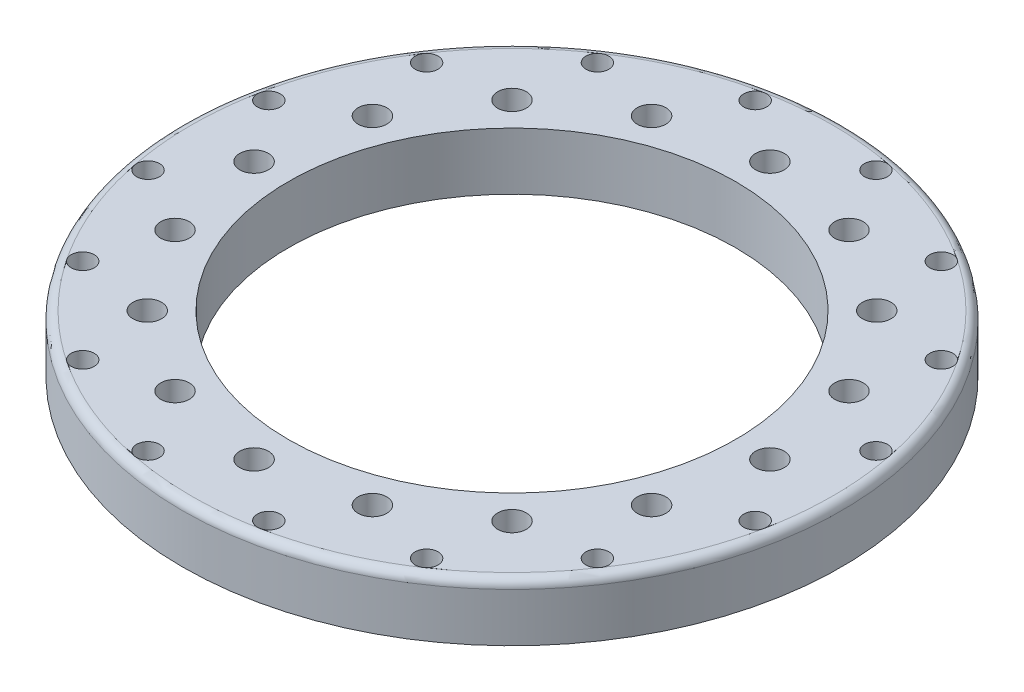
SolidWorks part; units mm, degrees
ref_plane "Front Plane" through (0, 0, 0) normal (0, 0, 1) x (1, 0, 0)
ref_plane "Top Plane" through (0, 0, 0) normal (0, 1, 0) x (1, 0, 0)
ref_plane "Right Plane" through (0, 0, 0) normal (1, 0, 0) x (0, 0, -1)
sketch "Sketch1" plane through (0, 0, 0) normal (0, 1, 0) x (1, 0, 0)
  line L0 (-10.5349, 52.9624) -> (0, 0) construction
  line L1 (0, 0) -> (24.6214, 0) construction
  circle A12 centre (0, 0) radius 39
  circle A13 centre (0, 0) radius 57.5
  circle A14 centre (0, 0) radius 54 construction
  circle A15 centre (-10.5349, 52.9624) radius 2
  circle A16 centre (10.5349, 52.9624) radius 2
  circle A17 centre (30.0008, 44.8994) radius 2
  circle A18 centre (44.8994, 30.0008) radius 2
  circle A19 centre (52.9624, 10.5349) radius 2
  circle A20 centre (52.9624, -10.5349) radius 2
  circle A21 centre (44.8994, -30.0008) radius 2
  circle A22 centre (30.0008, -44.8994) radius 2
  circle A23 centre (10.5349, -52.9624) radius 2
  circle A24 centre (-10.5349, -52.9624) radius 2
  circle A25 centre (-30.0008, -44.8994) radius 2
  circle A26 centre (-44.8994, -30.0008) radius 2
  circle A47 centre (-52.9624, -10.5349) radius 2
  circle A48 centre (-52.9624, 10.5349) radius 2
  circle A49 centre (-44.8994, 30.0008) radius 2
  circle A50 centre (-30.0008, 44.8994) radius 2
  point P21 (0, 0)
  point P28 (0, 0)
  point P56 (0, 0)
  point P60 (0, 0)
  dimension "D1" = 101.25
  dimension "D4" = 115
  dimension "D5" = 78
  dimension "D6" = 108
  dimension "D7" = 4
  dimension "D8" = 16
extrude "Boss-Extrude1" add sketch "Sketch1" along normal blind 10
sketch "Sketch2" plane through (0, 10, 0) normal (0, 1, 0) x (1, 0, 0)
  circle A0 centre (0, 0) radius 45 construction
  circle A1 centre (0, 45) radius 2.5
  circle A2 centre (17.2208, 41.5746) radius 2.5
  circle A3 centre (31.8198, 31.8198) radius 2.5
  circle A4 centre (41.5746, 17.2208) radius 2.5
  circle A5 centre (45, 0) radius 2.5
  circle A6 centre (41.5746, -17.2208) radius 2.5
  circle A7 centre (31.8198, -31.8198) radius 2.5
  circle A8 centre (17.2208, -41.5746) radius 2.5
  circle A9 centre (0, -45) radius 2.5
  circle A10 centre (-17.2208, -41.5746) radius 2.5
  circle A11 centre (-31.8198, -31.8198) radius 2.5
  circle A12 centre (-41.5746, -17.2208) radius 2.5
  circle A13 centre (-45, 0) radius 2.5
  circle A14 centre (-41.5746, 17.2208) radius 2.5
  circle A15 centre (-31.8198, 31.8198) radius 2.5
  circle A16 centre (-17.2208, 41.5746) radius 2.5
  point P27 (0, 0)
  dimension "D1" = 90
  dimension "D2" = 5
  dimension "D3" = 16
extrude "Cut-Extrude1" cut sketch "Sketch2" against normal blind 10
sketch "Sketch4" plane through (0, 0, 0) normal (0, 1, 0) x (1, 0, 0)
  circle A0 centre (0, 0) radius 45 construction
  circle A1 centre (0, 45) radius 5
  circle A2 centre (0, 45) radius 2.5
  circle A3 centre (17.2208, 41.5746) radius 2.5
  circle A4 centre (31.8198, 31.8198) radius 2.5
  circle A5 centre (41.5746, 17.2208) radius 2.5
  circle A6 centre (45, 0) radius 2.5
  circle A7 centre (41.5746, -17.2208) radius 2.5
  circle A8 centre (31.8198, -31.8198) radius 2.5
  circle A9 centre (17.2208, -41.5746) radius 2.5
  circle A10 centre (0, -45) radius 2.5
  circle A11 centre (-17.2208, -41.5746) radius 2.5
  circle A12 centre (-31.8198, -31.8198) radius 2.5
  circle A13 centre (17.2208, 41.5746) radius 5
  circle A14 centre (31.8198, 31.8198) radius 5
  circle A15 centre (41.5746, 17.2208) radius 5
  circle A16 centre (45, 0) radius 5
  circle A17 centre (41.5746, -17.2208) radius 5
  circle A18 centre (31.8198, -31.8198) radius 5
  circle A19 centre (17.2208, -41.5746) radius 5
  circle A20 centre (0, -45) radius 5
  circle A21 centre (-17.2208, -41.5746) radius 5
  circle A22 centre (-31.8198, -31.8198) radius 5
  circle A23 centre (-41.5746, -17.2208) radius 5
  circle A24 centre (-45, 0) radius 5
  circle A25 centre (-41.5746, 17.2208) radius 5
  circle A26 centre (-31.8198, 31.8198) radius 5
  circle A27 centre (-17.2208, 41.5746) radius 5
  circle A28 centre (-41.5746, -17.2208) radius 2.5
  circle A29 centre (-45, 0) radius 2.5
  circle A30 centre (-41.5746, 17.2208) radius 2.5
  circle A31 centre (-31.8198, 31.8198) radius 2.5
  circle A32 centre (-17.2208, 41.5746) radius 2.5
  point P29 (0, 0)
  point P50 (0, 0)
  dimension "D1" = 10
  dimension "D2" = 16
  dimension "D3" = 16
extrude "Boss-Extrude3" add sketch "Sketch4" against normal blind 0.4
fillet "Fillet1" radius 1.5 1 edges at (0, 10, 57.5)
